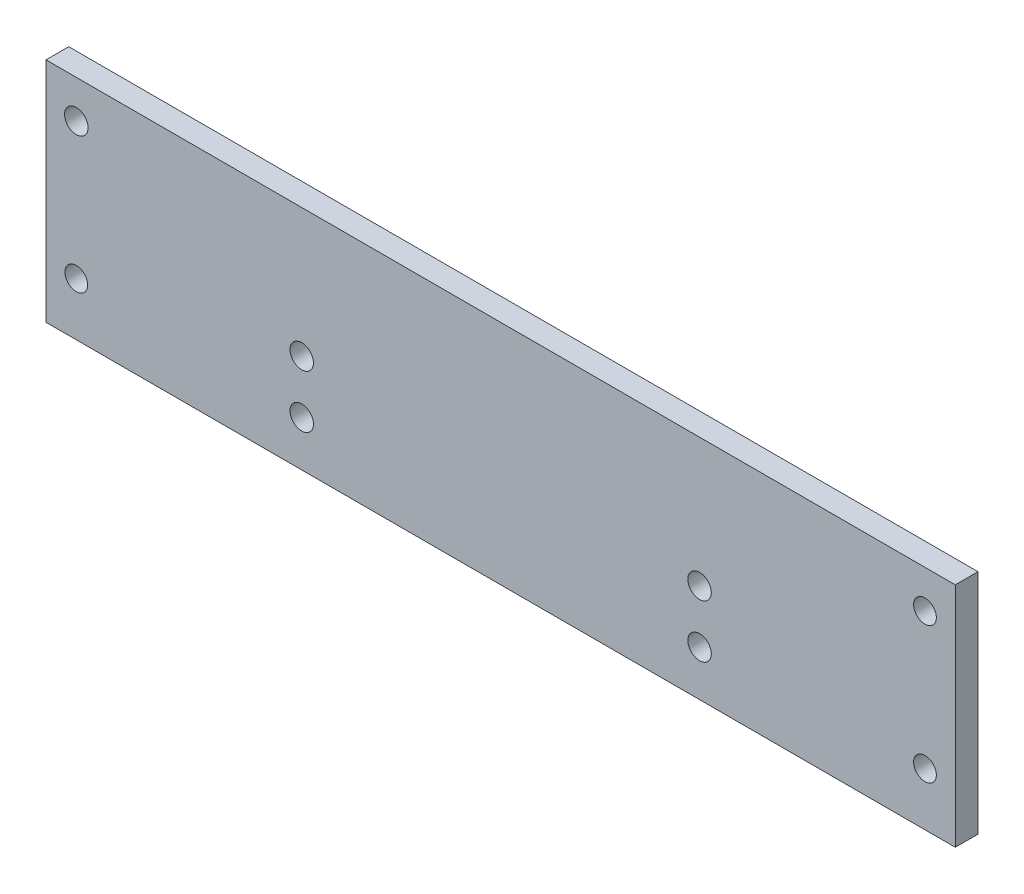
SolidWorks part; units mm, degrees
ref_plane "前视基准面" through (0, 0, 0) normal (0, 0, 1) x (1, 0, 0)
ref_plane "上视基准面" through (0, 0, 0) normal (0, 1, 0) x (1, 0, 0)
ref_plane "右视基准面" through (0, 0, 0) normal (1, 0, 0) x (0, 0, -1)
other "Configuration Table"
sketch "草图1" plane through (0, 0, 0) normal (0, 0, 1) x (1, 0, 0)
  line L1 (60, -15) -> (-60, -15)
  line L2 (60, -15) -> (60, 15)
  line L3 (60, 15) -> (-60, 15)
  line L4 (-60, -15) -> (-60, 15)
  line L5 (60, -15) -> (-60, 15) construction
  line L6 (60, 15) -> (-60, -15) construction
  point P0 (0, 0)
  dimension "D1" = 120
  dimension "D2" = 30
extrude "凸台-拉伸1" add sketch "草图1" along normal blind 3
sketch "草图3" plane through (0, 0, 0) normal (0, 0, -1) x (-1, 0, 0)
  line L2 (60, 15) -> (60, -15) construction
  line L3 (-60, 15) -> (60, 15) construction
  line L5 (-60, -15) -> (-60, 15) construction
  circle A0 centre (-56, 10) radius 1.5
  circle A1 centre (56, 10) radius 1.55
  dimension "D1" = 4
  dimension "D2" = 5
  dimension "D3" = 4
  dimension "D4" = 5
extrude "切除-拉伸2" cut sketch "草图3" against normal blind 10
sketch "草图4" plane through (0, 0, 3) normal (0, 0, 1) x (1, 0, 0)
  line L0 (0, 15) -> (0, 0) construction
  line L1 (60, 15) -> (-60, 15) construction
  line L2 (-60, -15) -> (60, -15) construction
  circle A0 centre (-26.25, -2) radius 1.55
  circle A1 centre (-26.25, -9) radius 1.55
  circle A2 centre (26.25, -9) radius 1.55
  circle A3 centre (26.25, -2) radius 1.55
  dimension "D1" = 3.1
  dimension "D2" = 3.1
  dimension "D5" = 6
  dimension "D3" = 26.25
  dimension "D4" = 26.25
  dimension "D6" = 13
sketch "草图5" plane through (0, 15, 0) normal (0, 1, 0) x (1, 0, 0)
  line L0 (0, 0) -> (0, -3) construction
  line L1 (60, -3) -> (-60, -3) construction
sketch "草图6" plane through (0, 0, 3) normal (0, 0, 1) x (1, 0, 0)
  line L0 (-56, 10) -> (-56, -8) construction
  line L1 (56, 10) -> (56, -8) construction
  circle A0 centre (-56, -8) radius 1.5
  circle A1 centre (56, -8) radius 1.5
  dimension "D1" = 3
  dimension "D2" = 18
extrude "切除-拉伸3" cut sketch "草图6" against normal blind 10
extrude "切除-拉伸4" cut sketch "草图4" against normal through all contours A0 | A1 | A3 | A2
